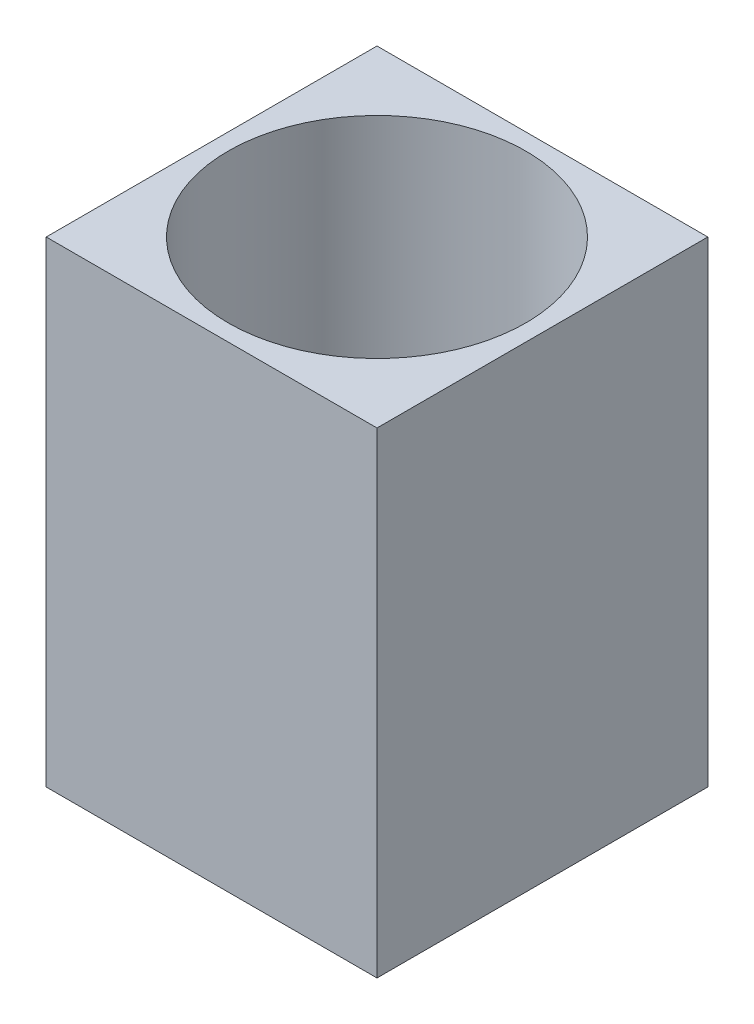
SolidWorks part; units mm, degrees
ref_plane "Front Plane" through (0, 0, 0) normal (0, 0, 1) x (1, 0, 0)
ref_plane "Top Plane" through (0, 0, 0) normal (0, 1, 0) x (1, 0, 0)
ref_plane "Right Plane" through (0, 0, 0) normal (1, 0, 0) x (0, 0, -1)
sketch "Sketch1" plane through (0, 0, 0) normal (0, 1, 0) x (1, 0, 0)
  line L1 (-317.5, -317.5) -> (317.5, -317.5)
  line L2 (-317.5, -317.5) -> (-317.5, 317.5)
  line L3 (-317.5, 317.5) -> (317.5, 317.5)
  line L4 (317.5, -317.5) -> (317.5, 317.5)
  circle A1 centre (0, 0) radius 285.75
  dimension "D4" = 571.5
  dimension "D2" = 635
  dimension "D3" = 635
extrude "Boss-Extrude1" add sketch "Sketch1" along normal mid plane 914.4
